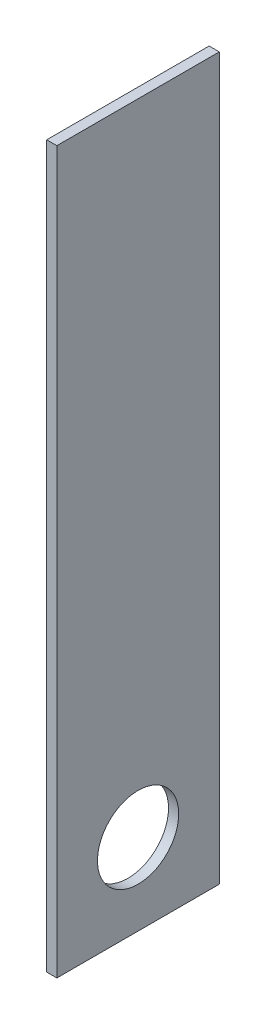
SolidWorks part; units mm, degrees
material "6063-O"
ref_plane "Front" through (0, 0, 0) normal (0, 0, 1) x (1, 0, 0)
ref_plane "Top" through (0, 0, 0) normal (0, 1, 0) x (1, 0, 0)
ref_plane "Right" through (0, 0, 0) normal (1, 0, 0) x (0, 0, -1)
sketch "Sketch1" plane through (0, 0, 0) normal (1, 0, 0) x (0, 0, -1)
  line L0 (0, 112.7125) -> (0, -112.7125) construction
  line L1 (-25.4, 112.7125) -> (25.4, 112.7125)
  line L2 (-25.4, 112.7125) -> (-25.4, -112.7125)
  line L3 (-25.4, -112.7125) -> (25.4, -112.7125)
  line L4 (25.4, 112.7125) -> (25.4, -112.7125)
  circle A0 centre (0, -87.3125) radius 12.7
  point P4 (0, 0)
  dimension "D3" = 25.4
  dimension "D1" = 50.8
  dimension "D2" = 225.425
  dimension "D4" = 25.4
extrude "Boss-Extrude1" add sketch "Sketch1" along normal blind 3.175
